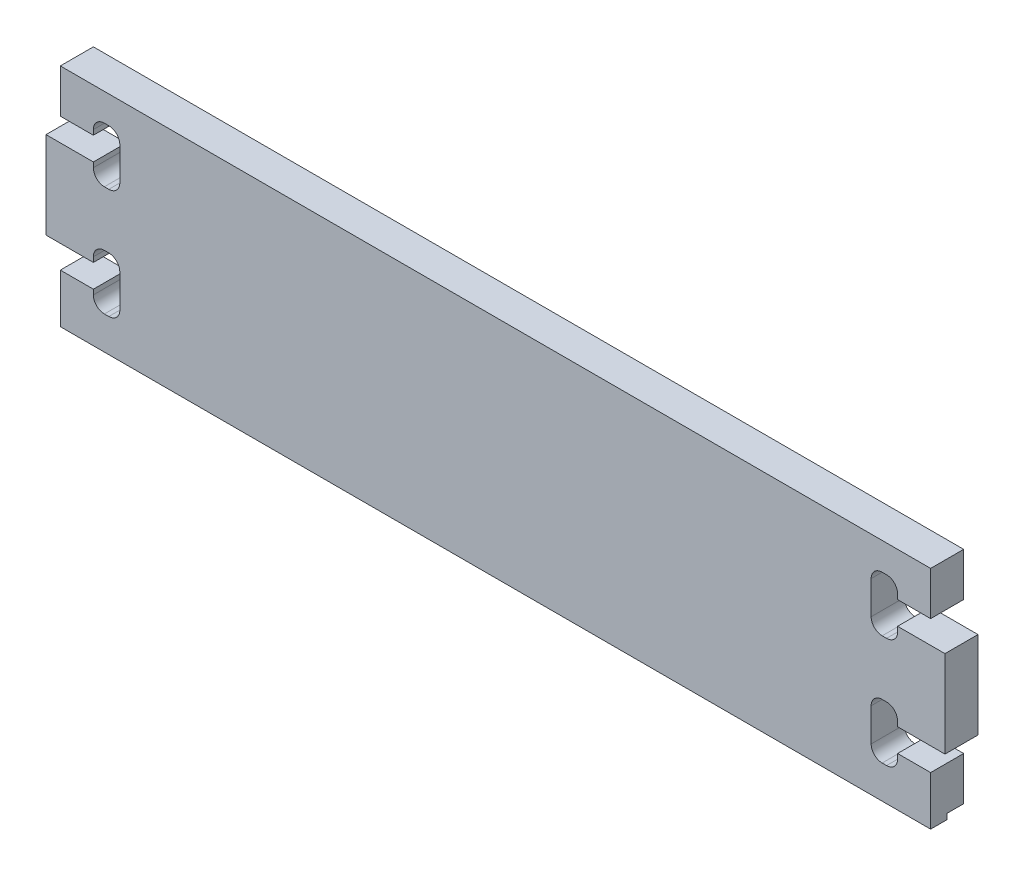
SolidWorks part; units mm, degrees
ref_plane "Front Plane" through (0, 0, 0) normal (0, 0, 1) x (1, 0, 0)
ref_plane "Top Plane" through (0, 0, 0) normal (0, 1, 0) x (1, 0, 0)
ref_plane "Right Plane" through (0, 0, 0) normal (1, 0, 0) x (0, 0, -1)
sketch "Sketch1" plane through (0, 0, 0) normal (0, 0, 1) x (1, 0, 0)
  line L0 (-39.5, 0) -> (39.5, 0) construction
  line L1 (-39.5, 10) -> (39.5, 10)
  line L2 (-39.5, 10) -> (-39.5, -10)
  line L3 (-39.5, -10) -> (39.5, -10)
  line L4 (39.5, 10) -> (39.5, -10)
  line L5 (-39.5, 10) -> (39.5, -10) construction
  line L6 (-39.5, -10) -> (39.5, 10) construction
  line L7 (0, 10) -> (0, -10) construction
  line L9 (-40.8, -3.95) -> (-39.5, -3.95)
  line L10 (-40.8, -3.95) -> (-40.8, 3.95)
  line L11 (-40.8, 3.95) -> (-39.5, 3.95)
  line L12 (-39.5, -3.95) -> (-39.5, 3.95)
  line L13 (-40.8, -3.95) -> (-39.5, 3.95) construction
  line L14 (-40.8, 3.95) -> (-39.5, -3.95) construction
  line L16 (40.8, 3.95) -> (39.5, 3.95)
  line L17 (40.8, -3.95) -> (40.8, 3.95)
  line L18 (40.8, -3.95) -> (39.5, -3.95)
  line L19 (-39.5, 5) -> (39.5, 5) construction
  line L20 (-35.3, 7.5) -> (-35.3, 2.5) construction
  line L21 (-36.5, 3.95) -> (-39.5, 3.95)
  line L22 (-36.5, 3.95) -> (-36.5, 6.05)
  line L23 (-36.5, 6.05) -> (-39.5, 6.05)
  line L24 (-39.5, 3.95) -> (-39.5, 6.05)
  line L25 (-36.5, 3.95) -> (-39.5, 6.05) construction
  line L26 (-36.5, 6.05) -> (-39.5, 3.95) construction
  line L27 (-34.1, 7.5) -> (-36.5, 7.5)
  line L28 (-34.1, 7.5) -> (-34.1, 2.5)
  line L29 (-34.1, 2.5) -> (-36.5, 2.5)
  line L30 (-36.5, 7.5) -> (-36.5, 2.5)
  line L31 (-34.1, 7.5) -> (-36.5, 2.5) construction
  line L32 (-34.1, 2.5) -> (-36.5, 7.5) construction
  line L33 (-34.1, -7.5) -> (-36.5, -7.5)
  line L34 (-34.1, -7.5) -> (-34.1, -2.5)
  line L35 (-34.1, -2.5) -> (-36.5, -2.5)
  line L36 (-36.5, -7.5) -> (-36.5, -2.5)
  line L37 (-36.5, -3.95) -> (-39.5, -3.95)
  line L38 (-36.5, -6.05) -> (-39.5, -6.05)
  line L39 (36.5, 3.95) -> (39.5, 3.95)
  line L40 (36.5, 6.05) -> (39.5, 6.05)
  line L41 (36.5, 7.5) -> (36.5, 2.5)
  line L42 (34.1, 7.5) -> (36.5, 7.5)
  line L43 (34.1, 7.5) -> (34.1, 2.5)
  line L44 (34.1, 2.5) -> (36.5, 2.5)
  line L45 (34.1, -2.5) -> (36.5, -2.5)
  line L46 (34.1, -7.5) -> (34.1, -2.5)
  line L47 (34.1, -7.5) -> (36.5, -7.5)
  line L48 (36.5, -7.5) -> (36.5, -2.5)
  line L49 (36.5, -6.05) -> (39.5, -6.05)
  line L50 (36.5, -3.95) -> (39.5, -3.95)
  point P0 (0, 0)
  point P10 (-40.15, 0)
  point P15 (-38, 5)
  point P35 (-35.3, 5)
  dimension "D1" = 79
  dimension "D2" = 20
  dimension "D4" = 1.3
  dimension "D7" = 5
  dimension "D8" = 2.1
  dimension "D9" = 3
  dimension "D10" = 2.4
  dimension "D11" = 5
extrude "Base shape" add sketch "Sketch1" along normal blind 3 contours L4 L1 L2 L3 | L9 L2 L11 L10 | L16 L4 L18 L17 region at (0, 0, 0) region at (-40.15, 0, 0) region at (40.15, 0, 0)
sketch "Sketch4" plane through (0, -10, 0) normal (0, -1, 0) x (1, 0, 0)
  line L0 (39.5, 3) -> (39.5, 0) construction
  line L1 (-39.5, 3) -> (39.5, 3)
  line L2 (-39.5, 3) -> (-39.5, 1.5)
  line L3 (-39.5, 1.5) -> (39.5, 1.5)
  line L4 (39.5, 3) -> (39.5, 1.5)
extrude "Floor lip" add sketch "Sketch4" along normal blind 0.5
sketch "Sketch6" plane through (0, 0, 0) normal (0, 0, -1) x (-1, 0, 0)
  line L0 (0, 0) -> (0, -10) construction
  line L1 (39.5, -10) -> (-39.5, -10) construction
  line L2 (-4, -10) -> (4, -10) construction
  line L3 (39.5, -10) -> (-39.5, -10) construction
  line L4 (-4, -9) -> (4, -9)
  line L5 (-4, -11) -> (4, -11)
  arc A0 (-4, -9) -> (-4, -11) centre (-4, -10) ccw
  arc A1 (4, -11) -> (4, -9) centre (4, -10) ccw
  point P9 (0, -10)
  dimension "D1" = 2
  dimension "D2" = 8
extrude "Nail cutout" cut sketch "Sketch6" against normal up to surface (1.5 mm away) up to face at (0, -10.25, 1.5)
sketch "Sketch3" plane through (-40.8, 0, 0) normal (-1, 0, 0) x (0, 0, 1)
  line L0 (0, 6.05) -> (3, 3.95) construction
  line L1 (0, 6.05) -> (3, 6.05)
  line L2 (0, 6.05) -> (0, 3.95)
  line L3 (0, 3.95) -> (3, 3.95)
  line L4 (3, 6.05) -> (3, 3.95)
  line L5 (0, -3.95) -> (3, -6.05) construction
  line L6 (0, -3.95) -> (3, -3.95)
  line L7 (0, -3.95) -> (0, -6.05)
  line L8 (0, -6.05) -> (3, -6.05)
  line L9 (3, -3.95) -> (3, -6.05)
  point P6 (1.5, 5)
  point P13 (1.5, -5)
ref_axis "Tap axis top" through (-53.7846, 5, 1.5) along (1, 0, 0)
ref_axis "Tap axis bottom" through (-54.2844, -5, 1.5) along (1, 0, 0)
fillet "Mill fillets" radius 1 16 edges at (36.5, -7.5, 1.5) (36.5, 2.5, 1.5) (34.1, 2.5, 1.5) (34.1, -7.5, 1.5) (36.5, -2.5, 1.5) (36.5, 7.5, 1.5) (34.1, -2.5, 1.5) (34.1, 7.5, 1.5) (-36.5, -2.5, 1.5) (-34.1, -2.5, 1.5) (-34.1, -7.5, 1.5) (-36.5, -7.5, 1.5) (-36.5, 2.5, 1.5) (-34.1, 2.5, 1.5) (-34.1, 7.5, 1.5) (-36.5, 7.5, 1.5)
sketch "Sketch2" plane through (0, 0, 3) normal (0, 0, 1) x (1, 0, 0)
  circle A0 centre (0, 0) radius 5
  dimension "D1" = 10
extrude "Forward cut (temp)" [suppressed] cut sketch "Sketch2" against normal blind 0.1
